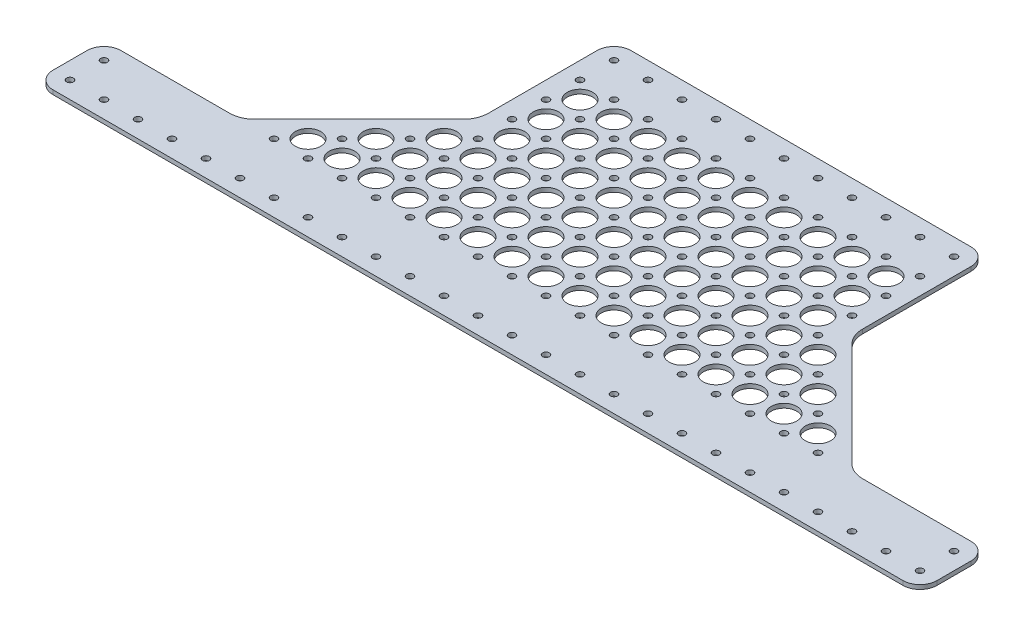
SolidWorks part; units mm, degrees
material "6061 Alloy"
ref_plane "Front Plane" through (0, 0, 0) normal (0, 0, 1) x (1, 0, 0)
ref_plane "Top Plane" through (0, 0, 0) normal (0, 1, 0) x (1, 0, 0)
ref_plane "Right Plane" through (0, 0, 0) normal (1, 0, 0) x (0, 0, -1)
sketch "Sketch1" plane through (0, 0, 0) normal (0, 1, 0) x (1, 0, 0)
  line L0 (0, 0) -> (0, 101.6)
  line L1 (0, 101.6) -> (279.4, 101.6)
  line L2 (279.4, 101.6) -> (279.4, 0)
  line L3 (279.4, 0) -> (368.3045, -88.9045)
  line L4 (368.3045, -88.9045) -> (469.9045, -88.9045)
  line L5 (469.9045, -88.9045) -> (469.9045, -419.1045)
  line L6 (469.9045, -419.1045) -> (368.3045, -419.1045)
  line L7 (368.3045, -419.1045) -> (279.4, -508.0091)
  line L8 (279.4, -508.0091) -> (279.4, -609.6091)
  line L9 (279.4, -609.6091) -> (0, -609.6091)
  line L10 (0, -609.6091) -> (0, -508.0091)
  line L11 (0, -508.0091) -> (-88.9045, -419.1045)
  line L12 (-88.9045, -419.1045) -> (-190.5045, -419.1045)
  line L13 (-190.5045, -419.1045) -> (-190.5045, -88.9045)
  line L14 (-190.5045, -88.9045) -> (-88.9045, -88.9045)
  line L15 (-88.9045, -88.9045) -> (0, 0)
  line L16 (-190.5045, -88.9045) -> (-177.8045, -88.9045)
  line L17 (-177.8045, -88.9045) -> (-177.8045, -419.1045) construction
  line L18 (-177.8045, -419.1045) -> (-190.5045, -419.1045)
  line L19 (-177.8045, -101.6045) -> (-177.8045, -127.0045) construction
  line L20 (139.7, -898.4) -> (139.7, 49101.6) construction
  line L21 (-966.4523, 88.9) -> (49033.5477, 88.9) construction
  line L22 (12.7, 88.9) -> (38.1, 88.9) construction
  line L23 (-1190.5045, -254.0045) -> (48809.4955, -254.0045) construction
  line L24 (-190.5045, -368.3045) -> (-88.9045, -368.3045) construction
  line L25 (-88.9045, -368.3045) -> (-88.9045, -419.1045) construction
  line L26 (-101.6045, -406.4045) -> (-127.0045, -406.4045) construction
  line L27 (-101.6045, -381.0045) -> (-127.0045, -381.0045) construction
  line L28 (-1102.5698, -114.3045) -> (48897.4302, -114.3045) construction
  line L29 (-1089.6596, -165.1045) -> (48910.3404, -165.1045) construction
  line L30 (-177.8045, -127.0045) -> (-152.4045, -127.0045) construction
  circle A0 centre (-177.8045, -101.6045) radius 2.54
  circle A1 centre (-177.8045, -127.0045) radius 2.54
  circle A2 centre (-177.8045, -152.4045) radius 2.54
  circle A3 centre (-177.8045, -177.8045) radius 2.54
  circle A4 centre (-177.8045, -203.2045) radius 2.54
  circle A5 centre (-177.8045, -228.6045) radius 2.54
  circle A6 centre (-177.8045, -254.0045) radius 2.54
  circle A7 centre (-177.8045, -279.4045) radius 2.54
  circle A8 centre (-177.8045, -304.8045) radius 2.54
  circle A9 centre (-177.8045, -330.2045) radius 2.54
  circle A10 centre (-177.8045, -355.6045) radius 2.54
  circle A11 centre (-177.8045, -381.0045) radius 2.54
  circle A12 centre (-177.8045, -406.4045) radius 2.54
  circle A13 centre (457.2045, -406.4045) radius 2.54
  circle A14 centre (457.2045, -381.0045) radius 2.54
  circle A15 centre (457.2045, -355.6045) radius 2.54
  circle A16 centre (457.2045, -330.2045) radius 2.54
  circle A17 centre (457.2045, -304.8045) radius 2.54
  circle A18 centre (457.2045, -279.4045) radius 2.54
  circle A19 centre (457.2045, -254.0045) radius 2.54
  circle A20 centre (457.2045, -228.6045) radius 2.54
  circle A21 centre (457.2045, -152.4045) radius 2.54
  circle A22 centre (457.2045, -177.8045) radius 2.54
  circle A23 centre (457.2045, -203.2045) radius 2.54
  circle A24 centre (457.2045, -127.0045) radius 2.54
  circle A25 centre (457.2045, -101.6045) radius 2.54
  circle A26 centre (12.7, 88.9) radius 2.54
  circle A27 centre (38.1, 88.9) radius 2.54
  circle A28 centre (63.5, 88.9) radius 2.54
  circle A29 centre (88.9, 88.9) radius 2.54
  circle A30 centre (114.3, 88.9) radius 2.54
  circle A31 centre (139.7, 88.9) radius 2.54
  circle A32 centre (165.1, 88.9) radius 2.54
  circle A33 centre (190.5, 88.9) radius 2.54
  circle A34 centre (215.9, 88.9) radius 2.54
  circle A35 centre (241.3, 88.9) radius 2.54
  circle A36 centre (266.7, 88.9) radius 2.54
  circle A37 centre (266.7, -596.9091) radius 2.54
  circle A38 centre (241.3, -596.9091) radius 2.54
  circle A39 centre (215.9, -596.9091) radius 2.54
  circle A40 centre (190.5, -596.9091) radius 2.54
  circle A41 centre (165.1, -596.9091) radius 2.54
  circle A42 centre (139.7, -596.9091) radius 2.54
  circle A43 centre (114.3, -596.9091) radius 2.54
  circle A44 centre (88.9, -596.9091) radius 2.54
  circle A45 centre (63.5, -596.9091) radius 2.54
  circle A46 centre (38.1, -596.9091) radius 2.54
  circle A47 centre (12.7, -596.9091) radius 2.54
  circle A48 centre (-101.6045, -381.0045) radius 2.54
  circle A49 centre (-101.6045, -406.4045) radius 2.54
  circle A50 centre (381.0045, -406.4045) radius 2.54
  circle A51 centre (381.0045, -381.0045) radius 2.54
  circle A52 centre (-127.0045, -406.4045) radius 2.54
  circle A53 centre (-152.4045, -406.4045) radius 2.54
  circle A54 centre (-127.0045, -381.0045) radius 2.54
  circle A55 centre (-152.4045, -381.0045) radius 2.54
  circle A56 centre (431.8045, -381.0045) radius 2.54
  circle A57 centre (406.4045, -381.0045) radius 2.54
  circle A58 centre (431.8045, -406.4045) radius 2.54
  circle A59 centre (406.4045, -406.4045) radius 2.54
  circle A60 centre (-152.4045, -127.0045) radius 2.54
  circle A61 centre (-152.4045, -152.4045) radius 2.54
  circle A62 centre (-127.0045, -127.0045) radius 2.54
  circle A63 centre (-127.0045, -152.4045) radius 2.54
  circle A64 centre (-101.6045, -127.0045) radius 2.54
  circle A65 centre (-101.6045, -152.4045) radius 2.54
  circle A66 centre (-76.2045, -127.0045) radius 2.54
  circle A67 centre (-76.2045, -152.4045) radius 2.54
  circle A68 centre (-50.8045, -127.0045) radius 2.54
  circle A69 centre (-50.8045, -152.4045) radius 2.54
  circle A70 centre (-25.4045, -127.0045) radius 2.54
  circle A71 centre (-25.4045, -152.4045) radius 2.54
  circle A72 centre (-0.0045, -127.0045) radius 2.54
  circle A73 centre (-0.0045, -152.4045) radius 2.54
  circle A74 centre (25.3955, -127.0045) radius 2.54
  circle A75 centre (25.3955, -152.4045) radius 2.54
  circle A76 centre (50.7955, -127.0045) radius 2.54
  circle A77 centre (50.7955, -152.4045) radius 2.54
  circle A78 centre (76.1955, -127.0045) radius 2.54
  circle A79 centre (76.1955, -152.4045) radius 2.54
  circle A80 centre (101.5955, -127.0045) radius 2.54
  circle A81 centre (101.5955, -152.4045) radius 2.54
  circle A82 centre (126.9955, -127.0045) radius 2.54
  circle A83 centre (126.9955, -152.4045) radius 2.54
  circle A84 centre (152.3955, -127.0045) radius 2.54
  circle A85 centre (152.3955, -152.4045) radius 2.54
  circle A86 centre (177.7955, -127.0045) radius 2.54
  circle A87 centre (177.7955, -152.4045) radius 2.54
  circle A88 centre (203.1955, -127.0045) radius 2.54
  circle A89 centre (203.1955, -152.4045) radius 2.54
  circle A90 centre (228.5955, -127.0045) radius 2.54
  circle A91 centre (228.5955, -152.4045) radius 2.54
  circle A92 centre (253.9955, -127.0045) radius 2.54
  circle A93 centre (253.9955, -152.4045) radius 2.54
  circle A94 centre (279.3955, -127.0045) radius 2.54
  circle A95 centre (279.3955, -152.4045) radius 2.54
  circle A96 centre (304.7955, -127.0045) radius 2.54
  circle A97 centre (304.7955, -152.4045) radius 2.54
  circle A98 centre (330.1955, -127.0045) radius 2.54
  circle A99 centre (330.1955, -152.4045) radius 2.54
  circle A100 centre (355.5955, -127.0045) radius 2.54
  circle A101 centre (355.5955, -152.4045) radius 2.54
  circle A102 centre (380.9955, -127.0045) radius 2.54
  circle A103 centre (380.9955, -152.4045) radius 2.54
  circle A104 centre (406.3955, -127.0045) radius 2.54
  circle A105 centre (406.3955, -152.4045) radius 2.54
  circle A106 centre (431.7955, -127.0045) radius 2.54
  circle A107 centre (431.7955, -152.4045) radius 2.54
  point P50 (139.7, 101.6)
  point P105 (-190.5045, -254.0045)
  dimension "D11" = 5.08
  dimension "D16" = 5.08
  dimension "D21" = 5.08
  dimension "D22" = 5.08
  dimension "D1" = 135
  dimension "D2" = 135
  dimension "D3" = 135
  dimension "D4" = 135
  dimension "D5" = 101.6
  dimension "D6" = 279.4
  dimension "D7" = 330.2
  dimension "D8" = 101.6
  dimension "D9" = 125.73
  dimension "D10" = 12.7
  dimension "D12" = 12.7
  dimension "D13" = 25.4
  dimension "D15" = 12.7
  dimension "D17" = 12.7
  dimension "D18" = 25.4
  dimension "D19" = 101.6
  dimension "D20" = 50.8
  dimension "D23" = 12.7
  dimension "D24" = 12.7
  dimension "D25" = 12.7
  dimension "D26" = 12.7
  dimension "D27" = 25.4
  dimension "D28" = 25.4
  dimension "D29" = 25.4
  dimension "D30" = 50.8
  dimension "D31" = 25.4
  dimension "D14" = 13
extrude "Boss-Extrude1" add sketch "Sketch1" along normal blind 3.175 contours L15 L14 L13 L12 L11 L10 L9 L8 L7 L6 L5 L4 L3 L2 L1 L0 A107 A106 A105 A104 A103 A102 A101 A100 A99 A98 A97 A96 A95 A94 A93 A92 region at (139.7, 0, 254.2329)
sketch "Sketch2" plane through (0, 0, 609.6091) normal (0, 0, 1) x (1, 0, 0)
  line L0 (279.4, 0) -> (0, 0) construction
  line L1 (-203.0133, -12.7) -> (508.1867, -12.7)
  line L2 (-203.0133, -12.7) -> (-203.0133, 12.7)
  line L3 (-203.0133, 12.7) -> (508.1867, 12.7)
  line L4 (508.1867, -12.7) -> (508.1867, 12.7)
  line L5 (-203.0133, -12.7) -> (508.1867, 12.7) construction
  line L6 (-203.0133, 12.7) -> (508.1867, -12.7) construction
  point P0 (152.5867, 0)
  dimension "D1" = 711.2
  dimension "D2" = 25.4
extrude "Cut-Extrude2" cut sketch "Sketch2" against normal blind 469.9
sketch "Sketch3" plane through (0, 3.175, 0) normal (0, 1, 0) x (1, 0, 0)
  line L0 (12.7, 88.9) -> (38.1, 88.9) construction
  line L1 (12.7, 88.9) -> (12.7, 63.5) construction
  line L2 (0, 0) -> (0, 101.6) construction
  line L3 (12.7, -88.9) -> (-12.7, -88.9) construction
  line L4 (12.7, -63.5) -> (-12.7, -63.5) construction
  line L5 (12.7, -38.1) -> (-12.7, -38.1) construction
  line L6 (0, 101.6) -> (279.4, 101.6) construction
  line L7 (266.7, -88.9) -> (292.1, -88.9) construction
  line L8 (266.7, -63.5) -> (292.1, -63.5) construction
  line L9 (266.7, -38.1) -> (292.1, -38.1) construction
  line L10 (25.4, 50.8) -> (50.8, 50.8) construction
  line L11 (25.4, 50.8) -> (25.4, 25.4) construction
  line L12 (279.4, 101.6) -> (279.4, 0) construction
  line L13 (25.4, -25.4) -> (0, -25.4) construction
  circle A0 centre (12.7, 88.9) radius 2.54
  circle A1 centre (38.1, 88.9) radius 2.54
  circle A2 centre (63.5, 88.9) radius 2.54
  circle A3 centre (88.9, 88.9) radius 2.54
  circle A4 centre (114.3, 88.9) radius 2.54
  circle A5 centre (139.7, 88.9) radius 2.54
  circle A6 centre (165.1, 88.9) radius 2.54
  circle A7 centre (190.5, 88.9) radius 2.54
  circle A8 centre (215.9, 88.9) radius 2.54
  circle A9 centre (241.3, 88.9) radius 2.54
  circle A10 centre (266.7, 88.9) radius 2.54
  circle A18 centre (12.7, 63.5) radius 2.54
  circle A19 centre (38.1, 63.5) radius 2.54
  circle A20 centre (63.5, 63.5) radius 2.54
  circle A21 centre (88.9, 63.5) radius 2.54
  circle A22 centre (114.3, 63.5) radius 2.54
  circle A23 centre (139.7, 63.5) radius 2.54
  circle A24 centre (165.1, 63.5) radius 2.54
  circle A25 centre (190.5, 63.5) radius 2.54
  circle A26 centre (215.9, 63.5) radius 2.54
  circle A27 centre (241.3, 63.5) radius 2.54
  circle A28 centre (266.7, 63.5) radius 2.54
  circle A36 centre (12.7, 38.1) radius 2.54
  circle A37 centre (38.1, 38.1) radius 2.54
  circle A38 centre (63.5, 38.1) radius 2.54
  circle A39 centre (88.9, 38.1) radius 2.54
  circle A40 centre (114.3, 38.1) radius 2.54
  circle A41 centre (139.7, 38.1) radius 2.54
  circle A42 centre (165.1, 38.1) radius 2.54
  circle A43 centre (190.5, 38.1) radius 2.54
  circle A44 centre (215.9, 38.1) radius 2.54
  circle A45 centre (241.3, 38.1) radius 2.54
  circle A46 centre (266.7, 38.1) radius 2.54
  circle A54 centre (12.7, 12.7) radius 2.54
  circle A55 centre (38.1, 12.7) radius 2.54
  circle A56 centre (63.5, 12.7) radius 2.54
  circle A57 centre (88.9, 12.7) radius 2.54
  circle A58 centre (114.3, 12.7) radius 2.54
  circle A59 centre (139.7, 12.7) radius 2.54
  circle A60 centre (165.1, 12.7) radius 2.54
  circle A61 centre (190.5, 12.7) radius 2.54
  circle A62 centre (215.9, 12.7) radius 2.54
  circle A63 centre (241.3, 12.7) radius 2.54
  circle A64 centre (266.7, 12.7) radius 2.54
  circle A72 centre (12.7, -12.7) radius 2.54
  circle A73 centre (38.1, -12.7) radius 2.54
  circle A74 centre (63.5, -12.7) radius 2.54
  circle A75 centre (88.9, -12.7) radius 2.54
  circle A76 centre (114.3, -12.7) radius 2.54
  circle A77 centre (139.7, -12.7) radius 2.54
  circle A78 centre (165.1, -12.7) radius 2.54
  circle A79 centre (190.5, -12.7) radius 2.54
  circle A80 centre (215.9, -12.7) radius 2.54
  circle A81 centre (241.3, -12.7) radius 2.54
  circle A82 centre (266.7, -12.7) radius 2.54
  circle A90 centre (12.7, -38.1) radius 2.54
  circle A91 centre (38.1, -38.1) radius 2.54
  circle A92 centre (63.5, -38.1) radius 2.54
  circle A93 centre (88.9, -38.1) radius 2.54
  circle A94 centre (114.3, -38.1) radius 2.54
  circle A95 centre (139.7, -38.1) radius 2.54
  circle A96 centre (165.1, -38.1) radius 2.54
  circle A97 centre (190.5, -38.1) radius 2.54
  circle A98 centre (215.9, -38.1) radius 2.54
  circle A99 centre (241.3, -38.1) radius 2.54
  circle A100 centre (266.7, -38.1) radius 2.54
  circle A108 centre (12.7, -63.5) radius 2.54
  circle A109 centre (38.1, -63.5) radius 2.54
  circle A110 centre (63.5, -63.5) radius 2.54
  circle A111 centre (88.9, -63.5) radius 2.54
  circle A112 centre (114.3, -63.5) radius 2.54
  circle A113 centre (139.7, -63.5) radius 2.54
  circle A114 centre (165.1, -63.5) radius 2.54
  circle A115 centre (190.5, -63.5) radius 2.54
  circle A116 centre (215.9, -63.5) radius 2.54
  circle A117 centre (241.3, -63.5) radius 2.54
  circle A118 centre (266.7, -63.5) radius 2.54
  circle A126 centre (12.7, -88.9) radius 2.54
  circle A127 centre (38.1, -88.9) radius 2.54
  circle A128 centre (63.5, -88.9) radius 2.54
  circle A129 centre (88.9, -88.9) radius 2.54
  circle A130 centre (114.3, -88.9) radius 2.54
  circle A131 centre (139.7, -88.9) radius 2.54
  circle A132 centre (165.1, -88.9) radius 2.54
  circle A133 centre (190.5, -88.9) radius 2.54
  circle A134 centre (215.9, -88.9) radius 2.54
  circle A135 centre (241.3, -88.9) radius 2.54
  circle A136 centre (266.7, -88.9) radius 2.54
  circle A211 centre (-12.7, -88.9) radius 2.54
  circle A212 centre (-38.1, -88.9) radius 2.54
  circle A213 centre (-63.5, -88.9) radius 2.54
  circle A214 centre (-12.7, -63.5) radius 2.54
  circle A215 centre (-38.1, -63.5) radius 2.54
  circle A216 centre (-12.7, -38.1) radius 2.54
  circle A224 centre (292.1, -88.9) radius 2.54
  circle A225 centre (317.5, -88.9) radius 2.54
  circle A226 centre (342.9, -88.9) radius 2.54
  circle A227 centre (292.1, -63.5) radius 2.54
  circle A228 centre (317.5, -63.5) radius 2.54
  circle A229 centre (292.1, -38.1) radius 2.54
  circle A230 centre (25.4, 50.8) radius 9.525
  circle A231 centre (50.8, 50.8) radius 9.525
  circle A232 centre (292.1, 88.9) radius 2.54 [skipped]
  circle A233 centre (317.5, 88.9) radius 2.54 [skipped]
  circle A234 centre (342.9, 88.9) radius 2.54 [skipped]
  circle A235 centre (368.3, 88.9) radius 2.54 [skipped]
  circle A236 centre (393.7, 88.9) radius 2.54 [skipped]
  circle A237 centre (419.1, 88.9) radius 2.54 [skipped]
  circle A238 centre (444.5, 88.9) radius 2.54 [skipped]
  circle A239 centre (12.7, -114.3) radius 2.54 [skipped]
  circle A240 centre (38.1, -114.3) radius 2.54 [skipped]
  circle A241 centre (63.5, -114.3) radius 2.54 [skipped]
  circle A242 centre (88.9, -114.3) radius 2.54 [skipped]
  circle A243 centre (114.3, -114.3) radius 2.54 [skipped]
  circle A244 centre (139.7, -114.3) radius 2.54 [skipped]
  circle A245 centre (165.1, -114.3) radius 2.54 [skipped]
  circle A246 centre (190.5, -114.3) radius 2.54 [skipped]
  circle A247 centre (215.9, -114.3) radius 2.54 [skipped]
  circle A248 centre (241.3, -114.3) radius 2.54 [skipped]
  circle A249 centre (266.7, -114.3) radius 2.54 [skipped]
  circle A250 centre (76.2, 50.8) radius 9.525
  circle A251 centre (101.6, 50.8) radius 9.525
  circle A252 centre (127, 50.8) radius 9.525
  circle A253 centre (152.4, 50.8) radius 9.525
  circle A254 centre (177.8, 50.8) radius 9.525
  circle A255 centre (203.2, 50.8) radius 9.525
  circle A256 centre (228.6, 50.8) radius 9.525
  circle A257 centre (254, 50.8) radius 9.525
  circle A265 centre (50.8, 25.4) radius 9.525
  circle A266 centre (76.2, 25.4) radius 9.525
  circle A267 centre (101.6, 25.4) radius 9.525
  circle A268 centre (127, 25.4) radius 9.525
  circle A269 centre (152.4, 25.4) radius 9.525
  circle A270 centre (177.8, 25.4) radius 9.525
  circle A271 centre (203.2, 25.4) radius 9.525
  circle A272 centre (228.6, 25.4) radius 9.525
  circle A273 centre (254, 25.4) radius 9.525
  circle A281 centre (50.8, 0) radius 9.525
  circle A282 centre (76.2, 0) radius 9.525
  circle A283 centre (101.6, 0) radius 9.525
  circle A284 centre (127, 0) radius 9.525
  circle A285 centre (152.4, 0) radius 9.525
  circle A286 centre (177.8, 0) radius 9.525
  circle A287 centre (203.2, 0) radius 9.525
  circle A288 centre (228.6, 0) radius 9.525
  circle A289 centre (254, 0) radius 9.525
  circle A297 centre (50.8, -25.4) radius 9.525
  circle A298 centre (76.2, -25.4) radius 9.525
  circle A299 centre (101.6, -25.4) radius 9.525
  circle A300 centre (127, -25.4) radius 9.525
  circle A301 centre (152.4, -25.4) radius 9.525
  circle A302 centre (177.8, -25.4) radius 9.525
  circle A303 centre (203.2, -25.4) radius 9.525
  circle A304 centre (228.6, -25.4) radius 9.525
  circle A305 centre (254, -25.4) radius 9.525
  circle A306 centre (279.4, -25.4) radius 9.525
  circle A313 centre (50.8, -50.8) radius 9.525
  circle A314 centre (76.2, -50.8) radius 9.525
  circle A315 centre (101.6, -50.8) radius 9.525
  circle A316 centre (127, -50.8) radius 9.525
  circle A317 centre (152.4, -50.8) radius 9.525
  circle A318 centre (177.8, -50.8) radius 9.525
  circle A319 centre (203.2, -50.8) radius 9.525
  circle A320 centre (228.6, -50.8) radius 9.525
  circle A321 centre (254, -50.8) radius 9.525
  circle A322 centre (279.4, -50.8) radius 9.525
  circle A323 centre (304.8, -50.8) radius 9.525
  circle A329 centre (50.8, -76.2) radius 9.525
  circle A330 centre (76.2, -76.2) radius 9.525
  circle A331 centre (101.6, -76.2) radius 9.525
  circle A332 centre (127, -76.2) radius 9.525
  circle A333 centre (152.4, -76.2) radius 9.525
  circle A334 centre (177.8, -76.2) radius 9.525
  circle A335 centre (203.2, -76.2) radius 9.525
  circle A336 centre (228.6, -76.2) radius 9.525
  circle A337 centre (254, -76.2) radius 9.525
  circle A338 centre (279.4, -76.2) radius 9.525
  circle A339 centre (304.8, -76.2) radius 9.525
  circle A340 centre (330.2, -76.2) radius 9.525
  circle A345 centre (25.4, 25.4) radius 9.525
  circle A346 centre (25.4, 0) radius 9.525
  circle A347 centre (25.4, -25.4) radius 9.525
  circle A348 centre (25.4, -50.8) radius 9.525
  circle A349 centre (25.4, -76.2) radius 9.525
  circle A350 centre (279.4, 25.4) radius 9.525 [skipped]
  circle A351 centre (304.8, 25.4) radius 9.525 [skipped]
  circle A352 centre (330.2, 25.4) radius 9.525 [skipped]
  circle A353 centre (355.6, 25.4) radius 9.525 [skipped]
  circle A354 centre (381, 25.4) radius 9.525 [skipped]
  circle A355 centre (406.4, 25.4) radius 9.525 [skipped]
  circle A356 centre (431.8, 25.4) radius 9.525 [skipped]
  circle A357 centre (279.4, 0) radius 9.525 [skipped]
  circle A358 centre (304.8, 0) radius 9.525 [skipped]
  circle A359 centre (330.2, 0) radius 9.525 [skipped]
  circle A360 centre (355.6, 0) radius 9.525 [skipped]
  circle A361 centre (381, 0) radius 9.525 [skipped]
  circle A362 centre (406.4, 0) radius 9.525 [skipped]
  circle A363 centre (431.8, 0) radius 9.525 [skipped]
  circle A364 centre (304.8, 50.8) radius 9.525 [skipped]
  circle A365 centre (330.2, 50.8) radius 9.525 [skipped]
  circle A366 centre (355.6, 50.8) radius 9.525 [skipped]
  circle A367 centre (381, 50.8) radius 9.525 [skipped]
  circle A368 centre (406.4, 50.8) radius 9.525 [skipped]
  circle A369 centre (431.8, 50.8) radius 9.525 [skipped]
  circle A370 centre (279.4, 50.8) radius 9.525 [skipped]
  circle A371 centre (330.2, -25.4) radius 9.525 [skipped]
  circle A372 centre (355.6, -25.4) radius 9.525 [skipped]
  circle A373 centre (381, -25.4) radius 9.525 [skipped]
  circle A374 centre (406.4, -25.4) radius 9.525 [skipped]
  circle A375 centre (431.8, -25.4) radius 9.525 [skipped]
  circle A376 centre (381, -50.8) radius 9.525 [skipped]
  circle A377 centre (406.4, -50.8) radius 9.525 [skipped]
  circle A378 centre (431.8, -50.8) radius 9.525 [skipped]
  circle A379 centre (406.4, -76.2) radius 9.525 [skipped]
  circle A380 centre (431.8, -76.2) radius 9.525 [skipped]
  circle A381 centre (381, -76.2) radius 9.525 [skipped]
  circle A382 centre (355.6, -76.2) radius 9.525 [skipped]
  circle A383 centre (355.6, -50.8) radius 9.525 [skipped]
  circle A384 centre (330.2, -50.8) radius 9.525 [skipped]
  circle A385 centre (304.8, -25.4) radius 9.525 [skipped]
  circle A386 centre (0, -25.4) radius 9.525
  circle A387 centre (0, -50.8) radius 9.525
  circle A388 centre (0, -76.2) radius 9.525
  circle A390 centre (-25.4, -50.8) radius 9.525
  circle A391 centre (-25.4, -76.2) radius 9.525
  circle A394 centre (-50.8, -76.2) radius 9.525
  circle A395 centre (-50.8, -25.4) radius 9.525 [skipped]
  circle A396 centre (-50.8, -50.8) radius 9.525 [skipped]
  circle A397 centre (-25.4, -25.4) radius 9.525 [skipped]
  dimension "D1" = 5.08
  dimension "D6" = 19.05
  dimension "D2" = 25.4
  dimension "D4" = 25.4
  dimension "D7" = 25.4
  dimension "D8" = 25.4
  dimension "D9" = 25.4
  dimension "D10" = 25.4
  dimension "D11" = 25.4
  dimension "D12" = 25.4
  dimension "D13" = 25.4
  dimension "D14" = 50.8
  dimension "D16" = 25.4
  dimension "D17" = 25.4
  dimension "D19" = 25.4
  dimension "D20" = 25.4
  dimension "D3" = 18
  dimension "D5" = 9
  dimension "D18" = 17
  dimension "D15" = 6
  dimension "D21" = 4
extrude "Cut-Extrude3" cut sketch "Sketch3" against normal blind 3.175
fillet "Fillet1" radius 12.7 6 edges at (-190.5045, 1.5875, 88.9045) (-190.5045, 1.5875, 139.7091) (469.9045, 1.5875, 88.9045) (469.9045, 1.5875, 139.7091) (279.4, 1.5875, -101.6) (0, 1.5875, -101.6)
fillet "Fillet2" radius 19.05 4 edges at (368.3045, 1.5875, 88.9045) (279.4, 1.5875, 0) (-88.9045, 1.5875, 88.9045) (0, 1.5875, 0)
sketch "Sketch4" plane through (0, 0, 0) normal (0, -1, 0) x (1, 0, 0)
  line L0 (-1189.9314, 139.7091) -> (48810.0686, 139.7091) construction
  line L1 (-190.5045, -850.8511) -> (-190.5045, 49149.1489) construction
  line L4 (457.2045, 139.7091) -> (-177.8045, 139.7091) construction
  line L5 (-190.5045, 127.0091) -> (-190.5045, 101.6045) construction
  point P3 (-190.5045, 139.7091)
  point P5 (-443.3994, 105.3572)
